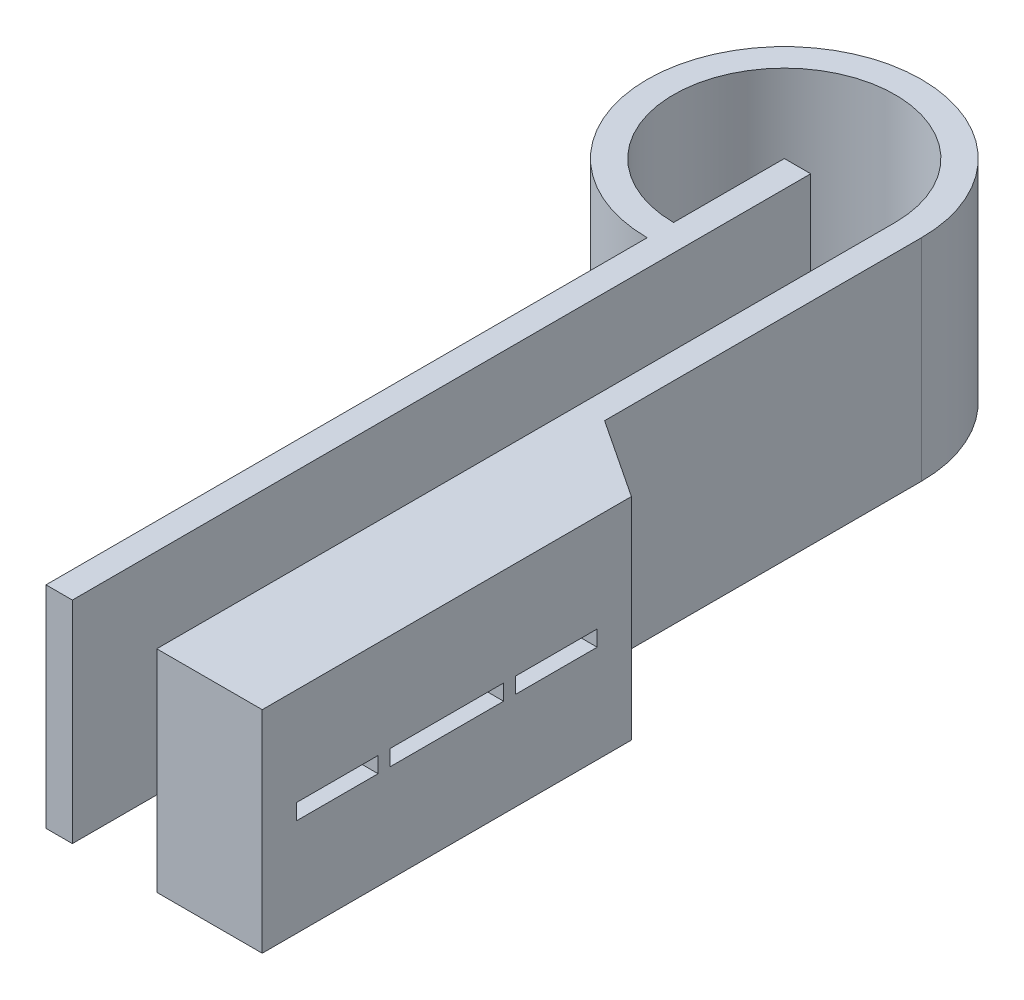
SolidWorks part; units mm, degrees
ref_plane "Front Plane" through (0, 0, 0) normal (0, 0, 1) x (1, 0, 0)
ref_plane "Top Plane" through (0, 0, 0) normal (0, 1, 0) x (1, 0, 0)
ref_plane "Right Plane" through (0, 0, 0) normal (1, 0, 0) x (0, 0, -1)
sketch "Sketch1" plane through (0, 0, 0) normal (0, 1, 0) x (1, 0, 0)
  line L0 (-30.8012, 22.7489) -> (-30.8012, -7.2931)
  line L1 (-43.8012, 22.7489) -> (-41.3012, 22.7489)
  line L2 (-43.8012, 22.7489) -> (-43.8012, -47.2511)
  line L3 (-43.8012, -47.2511) -> (-41.3012, -47.2511)
  line L4 (-41.3012, 22.7489) -> (-41.3012, -47.2511)
  line L5 (-33.3012, 22.7489) -> (-23.3012, 22.7489)
  line L6 (-33.3012, 22.7489) -> (-33.3012, -47.2511)
  line L7 (-33.3012, -47.2511) -> (-23.3012, -47.2511)
  line L8 (-23.3012, 22.7489) -> (-23.3012, -47.2511)
  line L9 (-30.8012, -7.2931) -> (-23.3012, -12.2511)
  arc A0 (-30.8012, 22.7489) -> (-43.8012, 9.7489) centre (-43.8012, 22.7489) ccw
  arc A1 (-33.3012, 22.7489) -> (-43.8012, 12.2489) centre (-43.8012, 22.7489) ccw
  point P8 (-42.5512, -47.2511)
  point P9 (-33.3012, -12.2511)
  dimension "D1" = 70
  dimension "D2" = 70
  dimension "D3" = 8
  dimension "D4" = 10
  dimension "D5" = 2.5
  dimension "D6" = 2.5
  dimension "D7" = 2.5
extrude "Boss-Extrude1" add sketch "Sketch1" along normal blind 20 contours A1 L5 L2 | L8 L5 L6 L7 | L2 L3 L4 L1 region at (-29.0207, 0, 22.2557) region at (-32.0512, 0, -23.1166)
sketch "Sketch2" plane through (-33.3012, 0, 0) normal (-1, 0, 0) x (0, 0, 1)
  line L0 (-9.7489, 20) -> (47.2511, 20) construction
  line L5 (47.2511, 20) -> (47.2511, 0) construction
  circle A0 centre (29.7511, 10) radius 2.6
  circle A1 centre (19.7511, 10) radius 4
  circle A2 centre (39.7511, 10) radius 4
  dimension "D5" = 10
  dimension "D7" = 10
  dimension "D1" = 10
  dimension "D2" = 10
  dimension "D6" = 10
  dimension "D8" = 17.5
extrude "Cut-Extrude2" cut sketch "Sketch2" against normal blind 8 contours A1 | A2 region at (-33.3012, 10, 19.7511)
sketch "Sketch3" plane through (-23.3012, 0, 0) normal (1, 0, 0) x (0, 0, -1)
  line L0 (-12.2511, 20) -> (-47.2511, 20) construction
  line L1 (-47.2511, 20) -> (-47.2511, 0) construction
  line L2 (-44.0074, 9.25) -> (-36.2673, 9.25)
  line L11 (-44.0074, 9.25) -> (-44.0074, 10.75)
  line L12 (-44.0074, 10.75) -> (-36.2673, 10.75)
  line L13 (-36.2673, 9.25) -> (-36.2673, 10.75)
  line L14 (-44.0074, 9.25) -> (-36.2673, 10.75) construction
  line L19 (-44.0074, 10.75) -> (-36.2673, 9.25) construction
  line L20 (-35.1373, 9.25) -> (-24.3649, 9.25)
  line L21 (-35.1373, 9.25) -> (-35.1373, 10.75)
  line L22 (-35.1373, 10.75) -> (-24.3649, 10.75)
  line L23 (-24.3649, 9.25) -> (-24.3649, 10.75)
  line L24 (-35.1373, 9.25) -> (-24.3649, 10.75) construction
  line L25 (-35.1373, 10.75) -> (-24.3649, 9.25) construction
  line L26 (-23.2349, 9.25) -> (-15.4949, 9.25)
  line L27 (-23.2349, 9.25) -> (-23.2349, 10.75)
  line L28 (-23.2349, 10.75) -> (-15.4949, 10.75)
  line L29 (-15.4949, 9.25) -> (-15.4949, 10.75)
  line L30 (-23.2349, 9.25) -> (-15.4949, 10.75) construction
  line L31 (-23.2349, 10.75) -> (-15.4949, 9.25) construction
  point P4 (-29.7511, 10)
  dimension "D1" = 1.5
  dimension "D2" = 1.5
  dimension "D3" = 1.13
  dimension "D4" = 1.13
  dimension "D5" = 1.5
  dimension "D6" = 0
  dimension "D7" = 10
  dimension "D8" = 17.5
extrude "Cut-Extrude4" cut sketch "Sketch3" against normal blind 10 contours L26 L29 L28 L27 | L20 L23 L22 L21 | L2 L13 L12 L11 region at (-23.3012, 10, 40.1373) region at (-23.3012, 10, 29.7511) region at (-23.3012, 10, 19.3649)
sketch "Sketch4" plane through (-33.3012, 0, 0) normal (-1, 0, 0) x (0, 0, 1)
  line L0 (47.2511, 20) -> (47.2511, 0) construction
  line L7 (24.7511, 17.5) -> (34.7511, 17.5)
  line L8 (24.7511, 17.5) -> (24.7511, 2.5)
  line L9 (24.7511, 2.5) -> (34.7511, 2.5)
  line L10 (34.7511, 17.5) -> (34.7511, 2.5)
  line L11 (24.7511, 17.5) -> (34.7511, 2.5) construction
  line L12 (24.7511, 2.5) -> (34.7511, 17.5) construction
  line L13 (-9.7489, 20) -> (47.2511, 20) construction
  point P0 (29.7511, 10)
  dimension "D1" = 17.5
  dimension "D2" = 10
  dimension "D3" = 10
  dimension "D4" = 15
extrude "Cut-Extrude5" cut sketch "Sketch4" against normal blind 2
